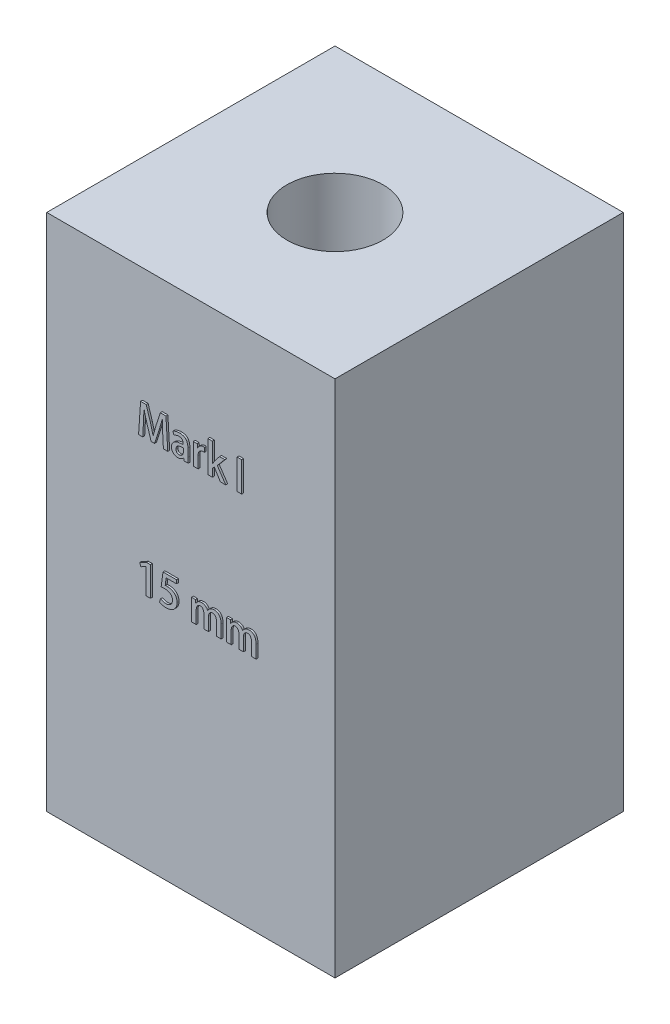
SolidWorks part; units mm, degrees
ref_plane "Alzado" through (0, 0, 0) normal (0, 0, 1) x (1, 0, 0)
ref_plane "Planta" through (0, 0, 0) normal (0, 1, 0) x (1, 0, 0)
ref_plane "Vista lateral" through (0, 0, 0) normal (1, 0, 0) x (0, 0, -1)
sketch "Croquis1" plane through (0, 0, 0) normal (0, 1, 0) x (1, 0, 0)
  line L1 (-7.5, 7.5) -> (7.5, 7.5)
  line L2 (-7.5, 7.5) -> (-7.5, -7.5)
  line L3 (-7.5, -7.5) -> (7.5, -7.5)
  line L4 (7.5, 7.5) -> (7.5, -7.5)
  line L5 (-7.5, 7.5) -> (7.5, -7.5) construction
  line L6 (-7.5, -7.5) -> (7.5, 7.5) construction
  circle A0 centre (0, 0) radius 2.5
  point P0 (0, 0)
  dimension "D1" = 5
  dimension "D2" = 15
extrude "Saliente-Extruir1" add sketch "Croquis1" along normal blind 27
sketch "Croquis2" plane through (0, 0, 7.5) normal (0, 0, 1) x (1, 0, 0)
  text T0 "Mark I\r\n \r\n15 mm" font "@Adobe Heiti Std R" height in points 5
split line "Línea de partición1"
extrude "Saliente-Extruir2" add sketch "Croquis2<2>" along normal blind 0.1
sketch "Croquis2<2>" plane through (0, 0, 7.5) normal (0, 0, 1) x (1, 0, 0) same geometry as "Croquis2"
